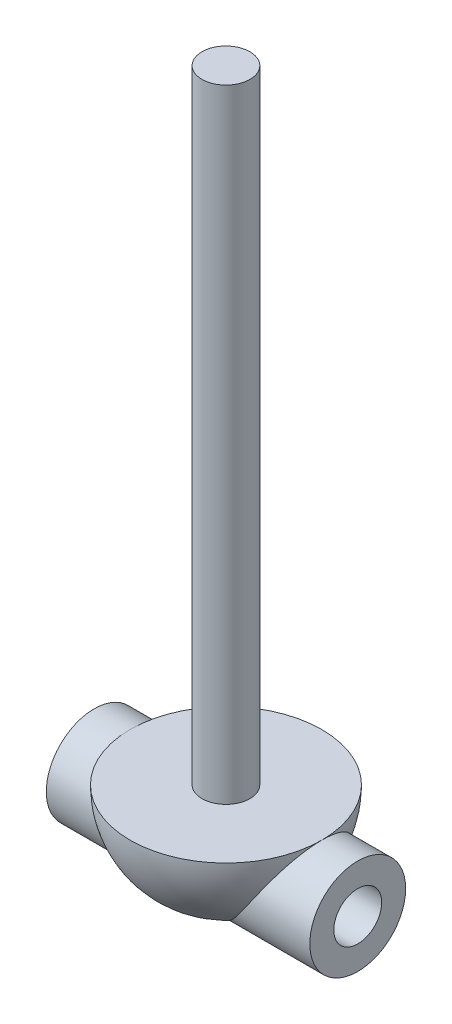
SolidWorks part; units mm, degrees
material "3.1355 (EN-AW 2024)"
ref_plane "Płaszczyzna przednia" through (0, 0, 0) normal (0, 0, 1) x (1, 0, 0)
ref_plane "Płaszczyzna górna" through (0, 0, 0) normal (0, 1, 0) x (1, 0, 0)
ref_plane "Płaszczyzna prawa" through (0, 0, 0) normal (1, 0, 0) x (0, 0, -1)
sketch "Szkic3" plane through (0, 0, 0) normal (0, 1, 0) x (1, 0, 0)
  line L0 (0, 20) -> (0, -20)
  arc A0 (0, 20) -> (0, -20) centre (0, 0) cw
  dimension "D1" = 20
revolve "Obrót1" add sketch "Szkic3" angle 180 about L0 reverse direction yes
sketch "Szkic4" plane through (0, 0, 0) normal (1, 0, 0) x (0, 0, -1)
  line L0 (20, 0) -> (-20, 0) construction
  circle A1 centre (0, -10) radius 10
  arc A2 (-20, 0) -> (20, 0) centre (0, 0) ccw construction
  point P7 (0, 0)
extrude "Dodanie-wyciągnięcie1" add sketch "Szkic4" along normal blind 27.5 and the other way blind 27.5
sketch "Szkic5" plane through (27.5, 0, 0) normal (1, 0, 0) x (0, 0, -1)
  circle A0 centre (0, -10) radius 5
  arc A1 (0, 0) -> (0, -20) centre (0, -10) ccw construction
  point P2 (0, 0)
  dimension "D1" = 10
extrude "Wytnij-wyciągnięcie1" cut sketch "Szkic5" against normal through all
sketch "Szkic6" plane through (0, 0, 0) normal (0, 1, 0) x (1, 0, 0)
  circle A0 centre (0, 0) radius 5
  dimension "D1" = 10
extrude "Dodanie-wyciągnięcie2" add sketch "Szkic6" along normal blind 130
